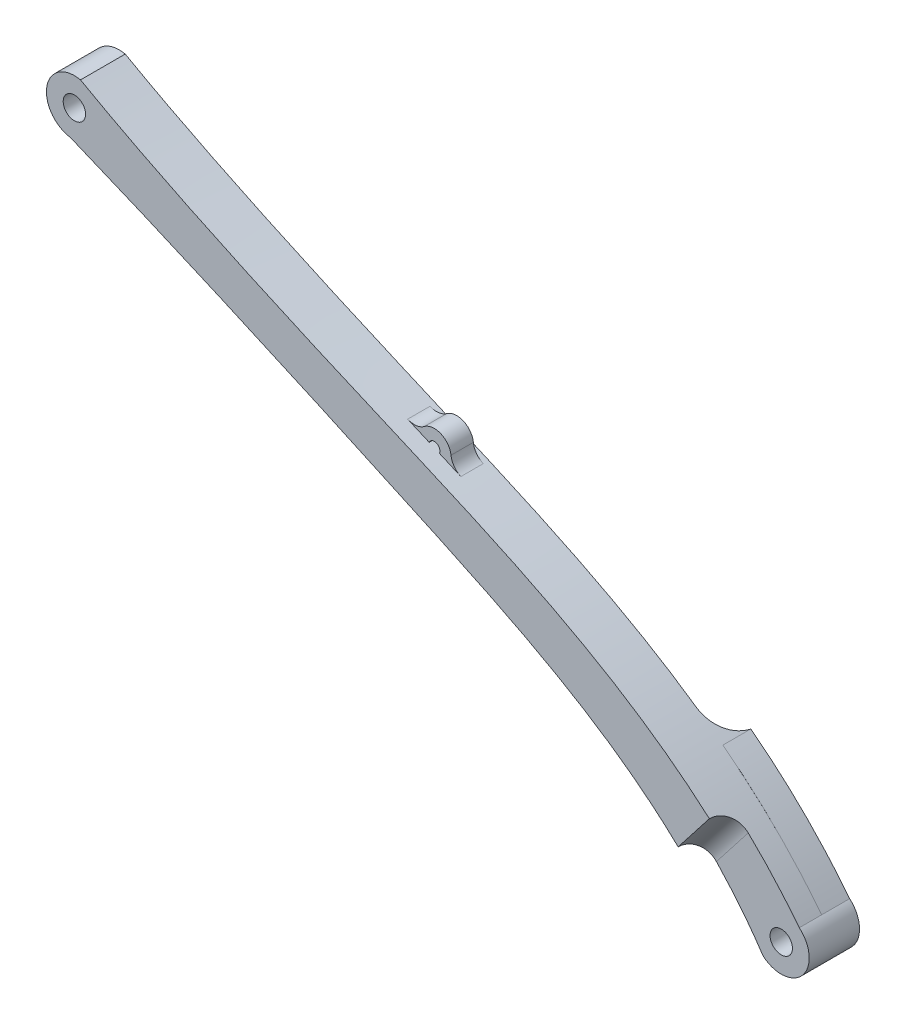
SolidWorks part; units mm, degrees
ref_plane "Спереди" through (0, 0, 0) normal (0, 0, 1) x (1, 0, 0)
ref_plane "Сверху" through (0, 0, 0) normal (0, 1, 0) x (1, 0, 0)
ref_plane "Справа" through (0, 0, 0) normal (1, 0, 0) x (0, 0, -1)
sketch "Sketch1" plane through (0, 0, 0) normal (0, 0, 1) x (1, 0, 0)
  line L0 (-5.265, 31.0446) -> (-66.4711, 66.0312) construction
  line L5 (-66.4711, 66.0312) -> (-5.265, 31.0446) construction
  arc A2 (-65.9245, 68.4707) -> (-66.8315, 63.5573) centre (-66.4711, 66.0312) ccw
  arc A3 (-6.8817, 29.1377) -> (-3.6483, 32.9515) centre (-5.265, 31.0446) ccw
  circle A4 centre (-66.4711, 66.0312) radius 1
  circle A5 centre (-5.265, 31.0446) radius 1
  spline S0 degree 3 poles (-66.8315, 63.5573) (-57.1578, 59.6166) (-35.0639, 49.6872) (-13.8474, 39.6163) (-6.8817, 29.1377) knots 0 0 0 0 0.486443 1 1 1 1
  spline S1 degree 3 poles (-65.9245, 68.4707) (-58.2959, 64.1729) (-35.6807, 53.9862) (-12.8578, 44.7997) (-3.6483, 32.9515) knots 0 0 0 0 0.40468 1 1 1 1
  point P2 (-33.8849, 47.4733)
  dimension "D3" = 2
  dimension "D4" = 2.5
  dimension "D1" = 70.5
  dimension "D2" = 5
extrude "Boss-Extrude1" add sketch "Sketch1" along normal blind 4
sketch "Sketch3" plane through (0, 0, 0) normal (0, 0, -1) x (-1, 0, 0)
  line L0 (66.4711, 66.0312) -> (5.265, 31.0446) construction
sketch "Sketch5" [suppressed] plane through (0, 0, -3.8) normal (0, 0, -1) x (-1, 0, 0)
  line L0 (52.8991, 55.5053) -> (51.1646, 54.5096)
  line L1 (18.6419, 35.8407) -> (20.007, 35.4713)
  line L2 (20.007, 35.4713) -> (20.3765, 36.8364)
  line L3 (20.007, 35.4713) -> (19.5092, 36.3386) construction
  line L4 (20.8101, 37.0853) -> (22.1752, 36.7159)
  line L5 (22.1752, 36.7159) -> (22.5446, 38.081)
  line L6 (22.9783, 38.3299) -> (24.3434, 37.9605)
  line L7 (24.3434, 37.9605) -> (24.7128, 39.3256)
  line L8 (25.1464, 39.5745) -> (26.5115, 39.2051)
  line L9 (26.5115, 39.2051) -> (26.881, 40.5702)
  line L10 (27.3146, 40.8191) -> (28.6797, 40.4497)
  line L11 (28.6797, 40.4497) -> (29.0492, 41.8148)
  line L12 (29.4828, 42.0637) -> (30.8479, 41.6943)
  line L13 (30.8479, 41.6943) -> (31.2173, 43.0594)
  line L14 (31.651, 43.3083) -> (33.0161, 42.9389)
  line L15 (33.0161, 42.9389) -> (33.3855, 44.304)
  line L16 (33.8191, 44.5529) -> (35.1843, 44.1835)
  line L17 (35.1843, 44.1835) -> (35.5537, 45.5486)
  line L18 (35.9873, 45.7975) -> (37.3524, 45.4281)
  line L19 (37.3524, 45.4281) -> (37.7219, 46.7932)
  line L20 (38.1555, 47.0421) -> (39.5206, 46.6726)
  line L21 (39.5206, 46.6726) -> (39.89, 48.0378)
  line L22 (40.3237, 48.2867) -> (41.6888, 47.9172)
  line L23 (41.6888, 47.9172) -> (42.0582, 49.2823)
  line L24 (42.4919, 49.5313) -> (43.857, 49.1618)
  line L25 (43.857, 49.1618) -> (44.2264, 50.5269)
  line L26 (44.66, 50.7759) -> (46.0251, 50.4064)
  line L27 (46.0251, 50.4064) -> (46.3946, 51.7715)
  line L28 (46.8282, 52.0205) -> (48.1933, 51.651)
  line L29 (48.1933, 51.651) -> (48.5627, 53.0161)
  line L30 (48.9964, 53.265) -> (50.3615, 52.8956)
  line L31 (50.3615, 52.8956) -> (50.7309, 54.2607)
  line L32 (51.1646, 54.5096) -> (52.5297, 54.1402)
  line L33 (52.5297, 54.1402) -> (52.8991, 55.5053)
  line L34 (50.7309, 54.2607) -> (48.9964, 53.265)
  line L35 (48.5627, 53.0161) -> (46.8282, 52.0205)
  line L36 (46.3946, 51.7715) -> (44.66, 50.7759)
  line L37 (44.2264, 50.5269) -> (42.4919, 49.5313)
  line L38 (42.0582, 49.2823) -> (40.3237, 48.2867)
  line L39 (39.89, 48.0378) -> (38.1555, 47.0421)
  line L40 (37.7219, 46.7932) -> (35.9873, 45.7975)
  line L41 (35.5537, 45.5486) -> (33.8191, 44.5529)
  line L42 (33.3855, 44.304) -> (31.651, 43.3083)
  line L43 (31.2173, 43.0594) -> (29.4828, 42.0637)
  line L44 (20.3765, 36.8364) -> (18.6419, 35.8407)
  line L45 (22.5446, 38.081) -> (20.8101, 37.0853)
  line L46 (24.7128, 39.3256) -> (22.9783, 38.3299)
  line L47 (26.881, 40.5702) -> (25.1464, 39.5745)
  line L48 (29.0492, 41.8148) -> (27.3146, 40.8191)
  line L49 (55.0673, 56.7499) -> (53.3327, 55.7542)
  line L50 (53.3327, 55.7542) -> (54.6978, 55.3848)
  line L51 (54.6978, 55.3848) -> (55.0673, 56.7499)
  line L52 (57.2355, 57.9945) -> (55.5009, 56.9988) construction
  line L53 (55.5009, 56.9988) -> (56.866, 56.6294) construction
  line L54 (56.866, 56.6294) -> (57.2355, 57.9945) construction
  line L55 (59.4036, 59.2391) -> (57.6691, 58.2434) construction
  line L56 (57.6691, 58.2434) -> (59.0342, 57.874) construction
  line L57 (59.0342, 57.874) -> (59.4036, 59.2391) construction
  line L58 (52.8991, 55.5053) -> (55.0673, 56.7499) construction
  dimension "D1" = 1
  dimension "D4" = 2.5
  dimension "D2" = 16
  dimension "D3" = 4
extrude "Boss-Extrude3" [suppressed] add sketch "Sketch5" against normal up to surface (11.6 mm away)
sketch "Sketch6" plane through (0, 0, 0) normal (0, 0, -1) x (-1, 0, 0)
  line L4 (12.4817, 41.6798) -> (15.1726, 38.1668)
  circle A0 centre (5.265, 31.0446) radius 1
  arc A1 (3.6483, 32.9515) -> (6.8817, 29.1377) centre (5.265, 31.0446) ccw
  spline S0 degree 2 poles (3.6483, 32.9515) (7.5023, 37.8754) (12.4817, 41.6798) knots 0 0 0 1 1 1
  spline S1 degree 3 poles (3.6483, 32.9515) (12.8578, 44.7997) (35.6807, 53.9862) (58.2959, 64.1729) (65.9245, 68.4707) knots 0 0 0 0 0.59532 1 1 1 1 construction
  spline S2 degree 2 poles (6.8817, 29.1377) (10.3083, 34.2685) (15.1726, 38.1668) knots 0 0 0 1 1 1
  spline S3 degree 3 poles (66.8315, 63.5573) (57.1578, 59.6166) (35.0639, 49.6872) (13.8474, 39.6163) (6.8817, 29.1377) knots 0 0 0 0 0.486443 1 1 1 1 construction
  dimension "D1" = 2.5
extrude "Boss-Extrude4" add sketch "Sketch6" along normal blind 2.5
sketch "Sketch7" plane through (0, 0, 4) normal (0, 0, 1) x (1, 0, 0)
  line L5 (-13.3378, 34.704) -> (-7.6741, 41.9566)
  circle A0 centre (-5.265, 31.0446) radius 1
  arc A1 (-6.8817, 29.1377) -> (-3.6483, 32.9515) centre (-5.265, 31.0446) ccw
  spline S0 degree 2 poles (-3.6483, 32.9515) (-4.9434, 37.7737) (-7.6741, 41.9566) knots 0 0 0 1 1 1
  spline S2 degree 2 poles (-6.8817, 29.1377) (-10.0539, 31.9856) (-13.3378, 34.704) knots 0 0 0 1 1 1
extrude "Cut-Extrude2" cut sketch "Sketch7" against normal blind 2
sketch "Sketch8" [suppressed] plane through (13.3435, 23.2454, 0) normal (0.4978, 0.8673, 0) x (0.8673, -0.4978, 0)
  line L0 (-30.2361, -2) -> (-30.2361, -4)
  line L1 (-30.2361, -4) -> (-31.5956, -7.8)
  arc A0 (-30.9086, -4) -> (-31.486, -5) centre (-27.6423, -6.5526) ccw construction
  arc A1 (-31.486, -5) -> (-31.5956, -7.8) centre (-27.6423, -6.5526) ccw construction
  spline S0 degree 3 poles (-30.2361, -2) (-30.8049, -3.7955) (-32.3525, -5.7564) (-31.5956, -7.8) knots 0 0 0 0 1 1 1 1
extrude "Cut-Extrude3" [suppressed] cut sketch "Sketch8" against normal through all
fillet "Fillet2" [suppressed] radius 2.5
fillet "Fillet3" [suppressed] radius 2.5
fillet "Fillet4" radius 2 1 edges at (-11.0873, 37.5858, 2)
fillet "Fillet5" radius 3 1 edges at (-13.8271, 39.9233, 0)
sketch "Sketch9" plane through (0, 0, 0) normal (0, 0, -1) x (-1, 0, 0)
  line L0 (55.7382, 70.0567) -> (54.3972, 69.3845) construction
  line L1 (55.7382, 70.0567) -> (56.6014, 68.3347) construction
  line L2 (54.3972, 69.3845) -> (54.8454, 68.4906) construction
  line L3 (54.6213, 68.9375) -> (36.5992, 54.6476) construction
  circle A0 centre (54.6213, 68.9375) radius 0.5 construction
  circle A2 centre (54.6213, 68.9375) radius 1.5 construction
  circle A3 centre (35.7871, 54.2974) radius 0.5
  circle A4 centre (35.7871, 54.2974) radius 1.5
  spline S0 degree 3 poles (14.8683, 43.4287) (22.4614, 48.7133) (40.4434, 56.1315) (58.2959, 64.1729) (65.9245, 68.4707) knots 0.210596 0.210596 0.210596 0.210596 0.59532 1 1 1 1 construction
  dimension "D3" = 23
  dimension "D4" = 1
  dimension "D5" = 3
  dimension "D1" = 1.5
  dimension "D2" = 1
extrude "Boss-Extrude5" add sketch "Sketch9" against normal blind 2 from offset 0.5 offset against normal yes
fillet "Fillet6" radius 1.5 2 edges at (-37.1647, 54.8909, 1.5) (-34.4108, 53.701, 1.5)
